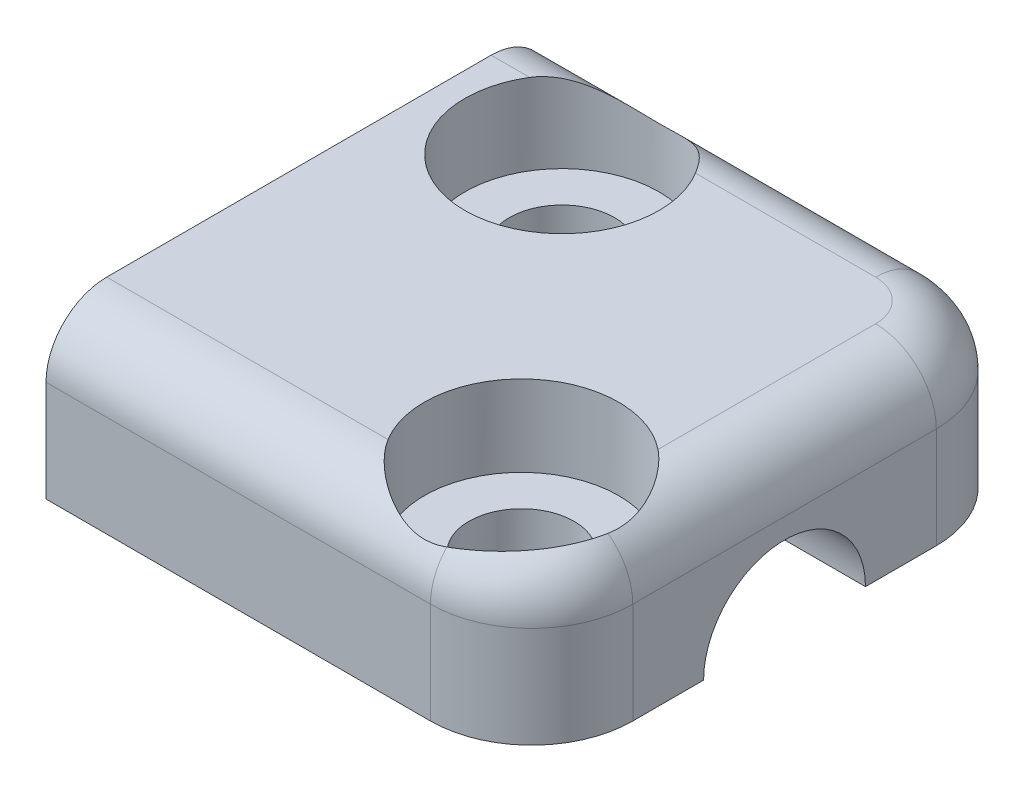
SolidWorks part; units mm, degrees
ref_plane "Front Plane" through (0, 0, 0) normal (0, 0, 1) x (1, 0, 0)
ref_plane "Top Plane" through (0, 0, 0) normal (0, 1, 0) x (1, 0, 0)
ref_plane "Right Plane" through (0, 0, 0) normal (1, 0, 0) x (0, 0, -1)
sketch "Sketch1" plane through (0, 0, 0) normal (0, 1, 0) x (1, 0, 0)
  line L1 (-12, 12.5) -> (12, 12.5)
  line L2 (-12, 12.5) -> (-12, -12.5)
  line L3 (-12, -12.5) -> (12, -12.5)
  line L4 (12, 12.5) -> (12, -12.5)
  line L5 (-12, 12.5) -> (12, -12.5) construction
  line L6 (-12, -12.5) -> (12, 12.5) construction
  point P0 (0, 0)
  dimension "D1" = 25
  dimension "D2" = 24
extrude "Boss-Extrude1" add sketch "Sketch1" along normal blind 8
sketch "Sketch2" plane through (-12, 0, 0) normal (-1, 0, 0) x (0, 0, 1)
  circle A0 centre (0, 0) radius 4
  dimension "D1" = 8
extrude "Cut-Extrude1" cut sketch "Sketch2" against normal through all
sketch "Sketch3" plane through (0, 0, 0) normal (0, -1, 0) x (1, 0, 0)
  line L0 (-6, -7) -> (6, 7) construction
  line L1 (-6, -7) -> (12.0808, -7) construction
  circle A0 centre (-6, -7) radius 2.6
  circle A1 centre (6, 7) radius 2.6
extrude "Cut-Extrude2" cut sketch "Sketch3" against normal through all
fillet "Fillet1" radius 3 3 edges at (0, 8, -12.5) (12, 8, 0) (0, 8, 12.5)
fillet "Fillet2" radius 5 4 edges at (11.1213, 7.1213, -11.6213) (11.1213, 7.1213, 11.6213) (12, 2.5, 12.5) (12, 2.5, -12.5)
sketch "Sketch4" plane through (0, 8, 0) normal (0, 1, 0) x (1, 0, 0)
  circle A0 centre (-6, 7) radius 4.8
  circle A1 centre (6, -7) radius 4.8
  dimension "D1" = 9.6
extrude "Cut-Extrude3" cut sketch "Sketch4" against normal blind 4
